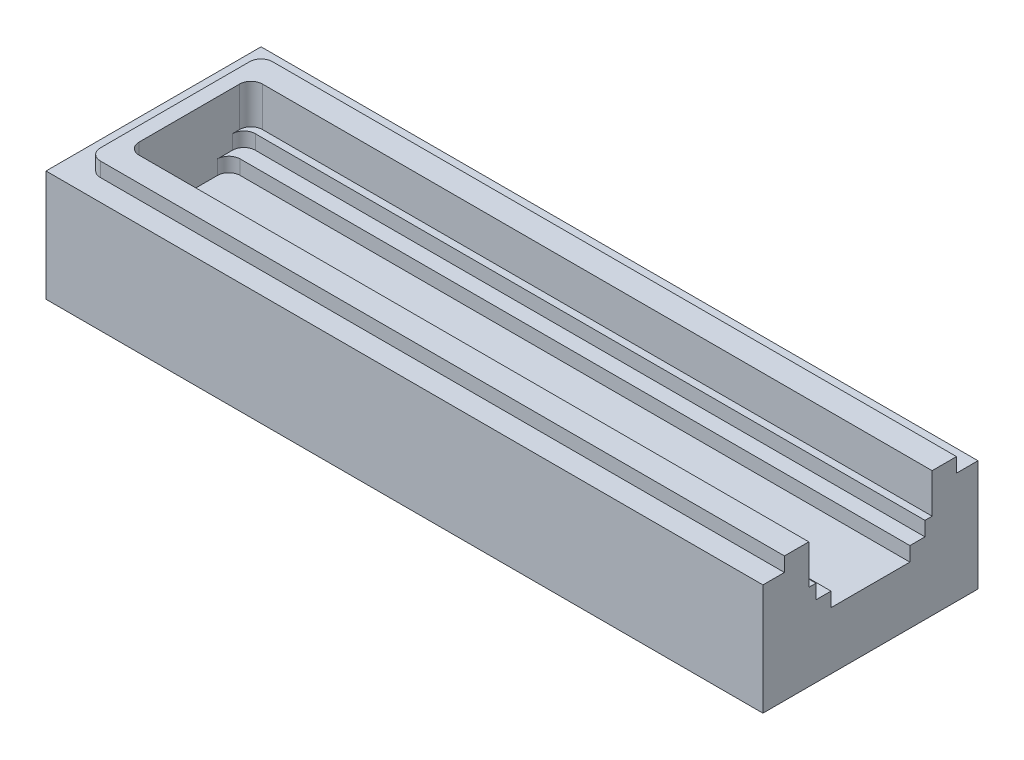
SolidWorks part; units mm, degrees
ref_plane "Front Plane" through (0, 0, 0) normal (0, 0, 1) x (1, 0, 0)
ref_plane "Top Plane" through (0, 0, 0) normal (0, 1, 0) x (1, 0, 0)
ref_plane "Right Plane" through (0, 0, 0) normal (1, 0, 0) x (0, 0, -1)
sketch "Sketch1" plane through (0, 0, 0) normal (0, 1, 0) x (1, 0, 0)
  line L1 (0, 15) -> (100, 15)
  line L2 (0, 15) -> (0, -15)
  line L3 (0, -15) -> (100, -15)
  line L4 (100, 15) -> (100, -15)
  point P4 (0, 0)
  dimension "D1" = 30
  dimension "D2" = 100
extrude "Boss-Extrude1" add sketch "Sketch1" along normal blind 20
sketch "Sketch2" plane through (0, 0, 0) normal (-1, 0, 0) x (0, 0, 1)
  line L0 (-15, 0) -> (15, 0) construction
  line L1 (-7.6, 25.5) -> (7.6, 25.5)
  line L2 (-7.6, 25.5) -> (-7.6, 10)
  line L3 (-7.6, 10) -> (7.6, 10)
  line L4 (7.6, 25.5) -> (7.6, 10)
  point P4 (0, 10)
  dimension "D1" = 15.2
  dimension "D2" = 15.5
  dimension "D3" = 10
extrude "Cut-Extrude1" cut sketch "Sketch2" against normal through all
sketch "Sketch3" plane through (0, 0, 0) normal (-1, 0, 0) x (0, 0, 1)
  line L0 (-7.6, 10) -> (7.6, 10) construction
  line L1 (-5.5, 10) -> (5.5, 10)
  line L2 (-5.5, 10) -> (-5.5, 8)
  line L3 (-5.5, 8) -> (5.5, 8)
  line L4 (5.5, 10) -> (5.5, 8)
  point P6 (0, 8)
  dimension "D1" = 2
  dimension "D2" = 11
extrude "Cut-Extrude2" cut sketch "Sketch3" against normal through all
sketch "Sketch4" plane through (0, 0, 0) normal (-1, 0, 0) x (0, 0, 1)
  line L0 (7.6, 10) -> (7.6, 20) construction
  line L1 (7.6, 12) -> (8.6, 12)
  line L2 (7.6, 12) -> (7.6, 20)
  line L3 (7.6, 20) -> (8.6, 20)
  line L4 (8.6, 12) -> (8.6, 20)
  line L5 (7.6, 20) -> (15, 20) construction
  line L6 (-7.6, 20) -> (-7.6, 10) construction
  line L7 (-7.6, 12) -> (-8.6, 12)
  line L8 (-7.6, 12) -> (-7.6, 20)
  line L9 (-7.6, 20) -> (-8.6, 20)
  line L10 (-8.6, 12) -> (-8.6, 20)
  line L11 (-15, 20) -> (-7.6, 20) construction
  line L12 (5.5, 10) -> (7.6, 10) construction
  point P16 (6.55, 10)
  dimension "D1" = 2
  dimension "D2" = 1
  dimension "D3" = 1
extrude "Cut-Extrude3" cut sketch "Sketch4" against normal through all
sketch "Sketch5" plane through (100, 0, 0) normal (1, 0, 0) x (0, 0, -1)
  line L0 (7.6, 10) -> (5.5, 10) construction
  line L1 (-12, 17.5) -> (12, 17.5)
  line L2 (-15, 17.5) -> (-15, 20)
  line L3 (-15, 20) -> (15, 20)
  line L4 (15, 17.5) -> (15, 20)
  line L5 (-15, 20) -> (-15, 0) construction
  line L6 (15, 20) -> (15, 0) construction
  line L7 (8.6, 20) -> (15, 20) construction
  line L10 (12, 17.5) -> (12, 15.5)
  line L11 (12, 15.5) -> (15, 15.5)
  line L12 (15, 17.5) -> (15, 15.5)
  line L13 (-15, 17.5) -> (-15, 15.5)
  line L14 (-15, 15.5) -> (-12, 15.5)
  line L15 (-12, 17.5) -> (-12, 15.5)
  dimension "D1" = 7.5
  dimension "D2" = 3
  dimension "D3" = 3
  dimension "D4" = 2
  dimension "D5" = 2
extrude "Cut-Extrude4" cut sketch "Sketch5" against normal through all
sketch "Sketch6" plane through (0, 17.5, 0) normal (0, 1, 0) x (1, 0, 0)
  line L0 (0, -8.6) -> (100, -8.6) construction
  line L1 (0, 8.6) -> (5, 8.6)
  line L2 (0, 8.6) -> (0, -8.6)
  line L3 (0, -8.6) -> (5, -8.6)
  line L4 (5, 8.6) -> (5, -8.6)
  dimension "D1" = 5
extrude "Boss-Extrude2" add sketch "Sketch6" against normal up to next
fillet "Fillet1" radius 1.5875 4 edges at (5, 9, 5.5) (5, 14.75, 8.6) (5, 9, -5.5) (5, 14.75, -8.6)
fillet "Fillet2" radius 1.5875 2 edges at (5.1127, 11, 7.6) (5.1127, 11, -7.6)
sketch "Sketch7" plane through (0, 17.5, 0) normal (0, 1, 0) x (1, 0, 0)
  line L0 (0, 12) -> (100, 12) construction
  line L1 (0, -12) -> (3, -12)
  line L2 (0, -12) -> (0, 12)
  line L3 (0, 12) -> (3, 12)
  line L4 (3, -12) -> (3, 12)
  dimension "D1" = 3
extrude "Cut-Extrude5" cut sketch "Sketch7" against normal up to surface (2 mm away) up to face at (50, 15.5, -13.5)
fillet "Fillet3" radius 1.5875 2 edges at (3, 16.5, 12) (3, 16.5, -12)
